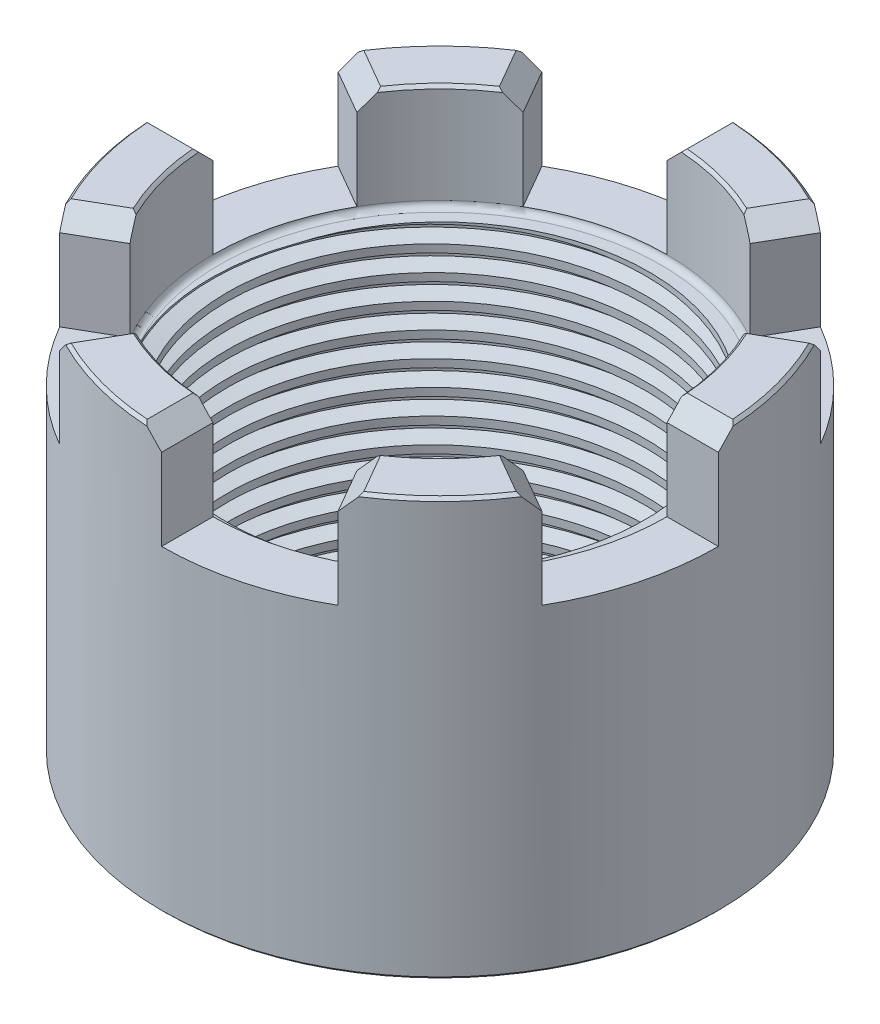
SolidWorks part; units mm, degrees
ref_plane "Front Plane" through (0, 0, 0) normal (0, 0, 1) x (1, 0, 0)
ref_plane "Top Plane" through (0, 0, 0) normal (0, 1, 0) x (1, 0, 0)
ref_plane "Right Plane" through (0, 0, 0) normal (1, 0, 0) x (0, 0, -1)
sketch "Sketch1" plane through (0, 0, 0) normal (0, 1, 0) x (1, 0, 0)
  circle A0 centre (0, 0) radius 35.56
  dimension "D1" = 71.12
extrude "Boss-Extrude1" add sketch "Sketch1" along normal blind 40.64
sketch "Sketch2" plane through (0, 40.64, 0) normal (0, 1, 0) x (1, 0, 0)
  circle A0 centre (0, 0) radius 26.7018
  dimension "D1" = 53.4035
extrude "Cut-Extrude1" cut sketch "Sketch2" against normal blind 67.31
sketch "Sketch3" plane through (0, 40.64, 0) normal (0, 1, 0) x (1, 0, 0)
  line L0 (-28.9941, 0) -> (-35.56, 0)
  line L1 (-25.1096, -14.4971) -> (-30.7959, -17.78)
  line L2 (-25.1096, 14.4971) -> (-30.7959, 17.78)
  line L3 (-14.497, 25.1096) -> (-17.78, 30.7959)
  line L4 (0, 28.9941) -> (0, 35.56)
  line L5 (14.4971, 25.1096) -> (17.78, 30.7959)
  line L6 (25.1096, 14.497) -> (30.7959, 17.78)
  line L7 (28.9941, 0) -> (35.56, 0)
  line L8 (25.1096, -14.4971) -> (30.7959, -17.78)
  line L9 (14.497, -25.1096) -> (17.78, -30.7959)
  line L10 (0, -28.9941) -> (0, -35.56)
  line L11 (-14.4971, -25.1096) -> (-17.78, -30.7959)
  arc A0 (-35.56, 0) -> (-30.7959, -17.78) centre (0, 0) ccw
  arc A1 (-28.9941, 0) -> (-25.1096, -14.4971) centre (0, 0) ccw
  arc A2 (-17.78, 30.7959) -> (-30.7959, 17.78) centre (0, 0) ccw
  arc A3 (-14.497, 25.1096) -> (-25.1096, 14.4971) centre (0, 0) ccw
  arc A4 (17.78, 30.7959) -> (0, 35.56) centre (0, 0) ccw
  arc A5 (14.4971, 25.1096) -> (0, 28.9941) centre (0, 0) ccw
  arc A6 (35.56, 0) -> (30.7959, 17.78) centre (0, 0) ccw
  arc A7 (28.9941, 0) -> (25.1096, 14.497) centre (0, 0) ccw
  arc A8 (17.78, -30.7959) -> (30.7959, -17.78) centre (0, 0) ccw
  arc A9 (14.497, -25.1096) -> (25.1096, -14.4971) centre (0, 0) ccw
  arc A10 (-17.78, -30.7959) -> (0, -35.56) centre (0, 0) ccw
  arc A11 (-14.4971, -25.1096) -> (0, -28.9941) centre (0, 0) ccw
  point P29 (0, 0)
  dimension "D2" = 57.9882
  dimension "D1" = 30
  dimension "D3" = 6
extrude "Boss-Extrude2" add sketch "Sketch3" along normal blind 12.7
chamfer "Chamfer1" distance 2.286 angle 45 1 edges at (0, 53.34, 32.2771)
chamfer "Chamfer2" distance 2.286 angle 45 1 edges at (-16.1385, 53.34, 27.9527)
chamfer "Chamfer3" distance 2.286 angle 45 1 edges at (-27.9527, 53.34, 16.1385)
chamfer "Chamfer4" distance 2.286 angle 45 1 edges at (16.1385, 53.34, 27.9527)
chamfer "Chamfer5" distance 2.286 angle 45 1 edges at (27.9527, 53.34, 16.1385)
chamfer "Chamfer6" distance 2.286 angle 45 1 edges at (32.277, 53.34, 0)
chamfer "Chamfer7" distance 2.286 angle 45 1 edges at (27.9527, 53.34, -16.1385)
chamfer "Chamfer8" distance 2.286 angle 45 1 edges at (16.1385, 53.34, -27.9527)
chamfer "Chamfer9" distance 2.286 angle 45 1 edges at (0, 53.34, -32.2771)
chamfer "Chamfer10" distance 2.286 angle 45 1 edges at (-16.1385, 53.34, -27.9527)
chamfer "Chamfer11" distance 2.286 angle 45 1 edges at (-27.9527, 53.34, -16.1385)
chamfer "Chamfer12" distance 2.286 angle 45 1 edges at (-32.2771, 53.34, 0)
chamfer "Chamfer13" distance 0.381 angle 45 1 edges at (9.2036, 53.34, -34.3483)
chamfer "Chamfer14" distance 0.381 angle 45 1 edges at (-25.1447, 53.34, -25.1447)
chamfer "Chamfer15" distance 0.381 angle 45 1 edges at (-34.3483, 53.34, 9.2036)
chamfer "Chamfer16" distance 0.381 angle 45 1 edges at (-9.2036, 53.34, 34.3483)
chamfer "Chamfer17" distance 0.381 angle 45 1 edges at (25.1447, 53.34, 25.1447)
chamfer "Chamfer18" distance 0.381 angle 45 1 edges at (34.3483, 53.34, -9.2036)
chamfer "Chamfer20" distance 0.381 angle 45 1 edges at (-28.0062, 53.34, 7.5042)
chamfer "Chamfer21" distance 0.381 angle 45 1 edges at (-7.5042, 53.34, 28.0062)
chamfer "Chamfer22" distance 0.381 angle 45 1 edges at (20.5019, 53.34, 20.5019)
chamfer "Chamfer23" distance 0.381 angle 45 1 edges at (-20.5019, 53.34, -20.5019)
chamfer "Chamfer24" distance 0.381 angle 45 1 edges at (7.5042, 53.34, -28.0062)
chamfer "Chamfer25" distance 0.381 angle 45 1 edges at (28.0062, 53.34, -7.5042)
chamfer "Chamfer26" distance 0.381 angle 45 1 edges at (0, 0, 35.56)
sketch "Sketch4" plane through (0, 40.64, 0) normal (0, 1, 0) x (1, 0, 0)
  circle A0 centre (0, 0) radius 28.9941
extrude "Cut-Extrude2" cut sketch "Sketch4" against normal blind 0.762
fillet "Fillet1" radius 0.762 1 edges at (0, 39.878, 28.9941)
thread "Thread3" pitch 3.175 method cut profile "Thread Profile4" start angle 1, offset 3.302, length 0, pitch 3.175, diameter 53.4035
ref_plane "Plane4" through (-26.6977, 43.18, -0.466) normal (0.0175, 0, -0.9998) x (0.9998, 0, 0.0175)
sketch "Thread Profile4" plane through (-26.6977, 43.18, -0.466) normal (0.0175, 0, -0.9998) x (0.9998, 0, 0.0175)
  line L0 (0, 0) -> (0, 3.175) construction
  line L11 (0, 0) -> (0, 2.1748)
  line L12 (0, 2.1748) -> (-1.9291, 1.6759)
  line L13 (-1.9291, 1.6759) -> (-1.9291, 0.4989)
  line L15 (-1.9291, 0.4989) -> (0, 0)
  line L17 (-1.9291, 1.0874) -> (0, 1.0874) construction
  point P2 (0, 0)
  dimension "D1" = 29
  dimension "Pitch" = 3.175
  dimension "Profile_Land" = 1.177
  dimension "Profile_Height" = 1.9291
